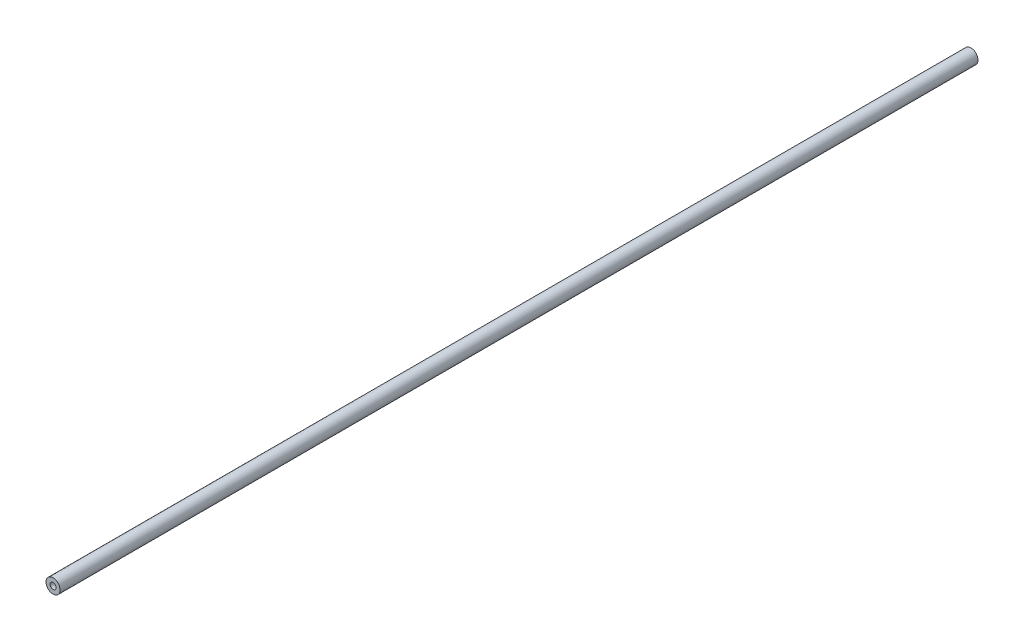
SolidWorks part; units mm, degrees
material "6061-T6 (SS)"
ref_plane "Front Plane" through (0, 0, 0) normal (0, 0, 1) x (1, 0, 0)
ref_plane "Top Plane" through (0, 0, 0) normal (0, 1, 0) x (1, 0, 0)
ref_plane "Right Plane" through (0, 0, 0) normal (1, 0, 0) x (0, 0, -1)
sketch "Sketch1" plane through (0, 0, 0) normal (0, 0, 1) x (1, 0, 0)
  circle A1 centre (0, 0) radius 4.7625
  dimension "D2" = 9.525
extrude "Boss-Extrude1" add sketch "Sketch1" along normal mid plane 618.6221
hole_wizard "#10-32 Tapped Hole1" positions "3DSketch1" profile "Sketch2" tap size "#10-32" standard "ANSI Inch"
sketch3d "3DSketch1"
  line L0 (0, 0, 309.311) -> (0, 0, -309.311) construction
  point P0 (0, 0, -309.311)
  point P4 (0, 0, 309.311)
sketch "Sketch2" plane through (0, 0, -309.311) normal (1, 0, 0) x (0, 1, 0)
  line L0 (0, 0) -> (0, 13.2428)
  line L1 (0, 13.2428) -> (2.0193, 12.0294)
  line L2 (2.0193, 12.0294) -> (2.0193, 0)
  line L5 (2.0193, 0) -> (0, 0)
  line L10 (0, 13.2428) -> (-2.0193, 12.0294) construction
  line L11 (0, -6.35) -> (0, 107.95) construction
  dimension "Tap Drill Dia." = 4.0386
  dimension "Tap Drill Depth" = 12.0294
  dimension "Drill Angle" = 118
cosmetic thread "Hole Thread1" parameters "D1"=9.652, "D2"=4.826
cosmetic thread "Hole Thread2" parameters "D1"=9.652, "D2"=4.826
